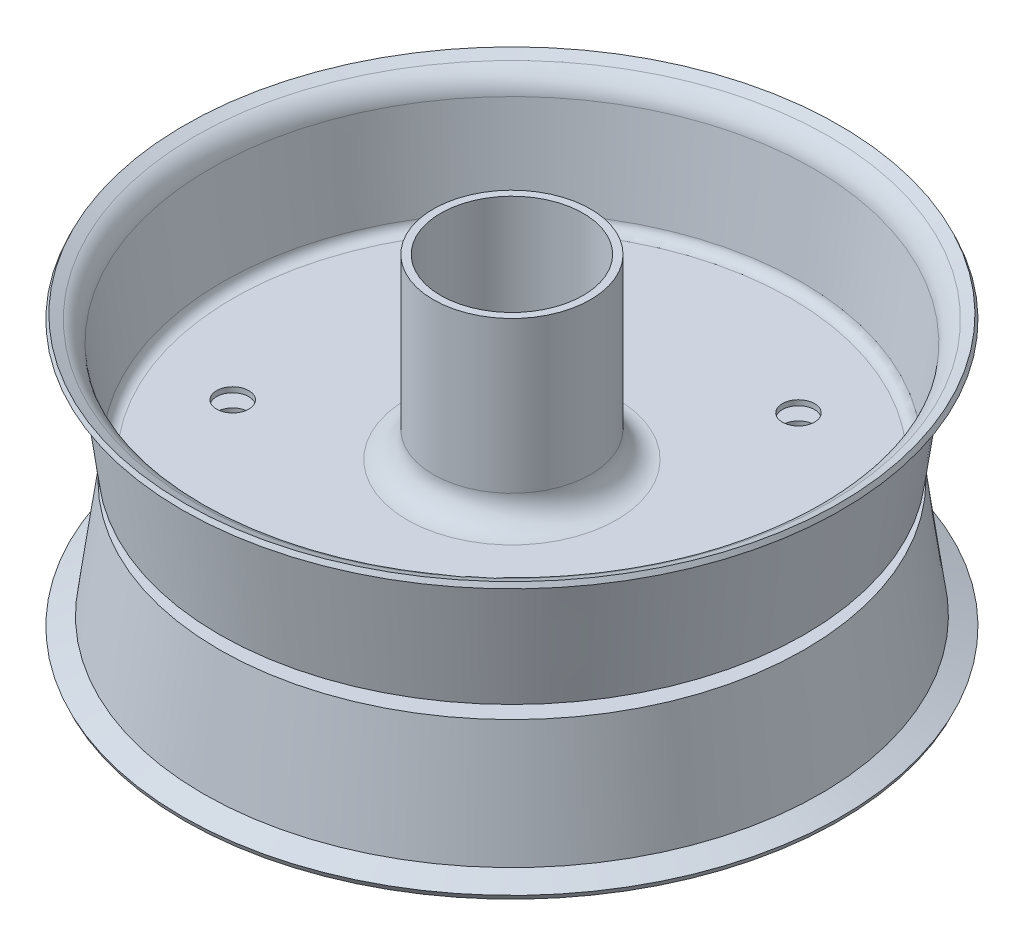
SolidWorks part; units mm, degrees
material "Alloy Steel"
ref_plane "Front Plane" through (0, 0, 0) normal (0, 0, 1) x (1, 0, 0)
ref_plane "Top Plane" through (0, 0, 0) normal (0, 1, 0) x (1, 0, 0)
ref_plane "Right Plane" through (0, 0, 0) normal (1, 0, 0) x (0, 0, -1)
sketch "Sketch1" plane through (0, 0, 0) normal (0, 1, 0) x (1, 0, 0)
  circle A0 centre (0, 0) radius 19.05
  circle A1 centre (0, 0) radius 17.272
  dimension "D1" = 34.544
  dimension "D2" = 38.1
extrude "Boss-Extrude1" add sketch "Sketch1" along normal blind 73.152
ref_plane "Plane1" through (0, 30.099, 0) normal (0, 1, 0) x (1, 0, 0)
sketch "Sketch3" plane through (0, 0, 0) normal (1, 0, 0) x (0, 0, -1)
  line L0 (-19.05, 30.099) -> (-69.85, 30.099)
  line L1 (20.955, 30.099) -> (-20.955, 30.099) construction
  line L2 (-69.85, 30.099) -> (-73.66, 58.039)
  line L3 (-73.66, 58.039) -> (-79.375, 60.579)
  line L4 (-19.05, 28.829) -> (-70.9586, 28.829)
  line L5 (-70.9586, 28.829) -> (-74.8227, 57.166)
  line L6 (-74.8227, 57.166) -> (-79.8908, 59.4185)
  line L7 (-79.375, 60.579) -> (-79.8908, 59.4185)
  line L8 (0, 73.152) -> (0, 28.829) construction
  line L9 (19.05, 73.152) -> (-19.05, 73.152) construction
  line L10 (-19.05, 28.829) -> (-19.05, 30.099)
  line L11 (-19.05, 73.152) -> (-19.05, 0) construction
  line L12 (0, 30.099) -> (-69.85, 30.099) construction
  line L13 (0, 28.829) -> (-70.9586, 28.829) construction
  point P18 (0, 0)
  dimension "D1" = 69.85
  dimension "D2" = 73.66
  dimension "D3" = 79.375
  dimension "D4" = 30.48
  dimension "D5" = 27.94
  dimension "D6" = 1.27
revolve "Revolve1" add sketch "Sketch3" angle 360 about L8
fillet "Fillet1" radius 6.35 1 edges at (0, 30.099, 19.05)
fillet "Fillet2" radius 2.54 1 edges at (0, 30.099, 69.85)
fillet "Fillet3" radius 6.35 1 edges at (0, 58.039, 73.66)
ref_plane "Plane2" through (0, 27.2415, 0) normal (0, -1, 0) x (-1, 0, 0)
sketch "Sketch2" plane through (0, 30.099, 0) normal (0, 1, 0) x (1, 0, 0)
  circle A0 centre (-34.6148, 37.4844) radius 3.9
  circle A1 centre (24.9533, 44.504) radius 3.9
  circle A2 centre (50.0368, -9.9795) radius 3.9
  circle A3 centre (5.9712, -50.6716) radius 3.9
  circle A4 centre (-46.3464, -21.3373) radius 3.9
  point P0 (-34.6148, 37.4844)
  point P14 (0, 0)
  dimension "D2" = 7.8
  dimension "D1" = 51.0222
  dimension "D3" = 5
extrude "Cut-Extrude1" cut sketch "Sketch2" against normal up to next
mirror "Mirror1" about plane through (0, 27.2415, 0) normal (0, -1, 0) of "Cut-Extrude1", "Fillet3", "Fillet2", "Fillet1", "Revolve1"
